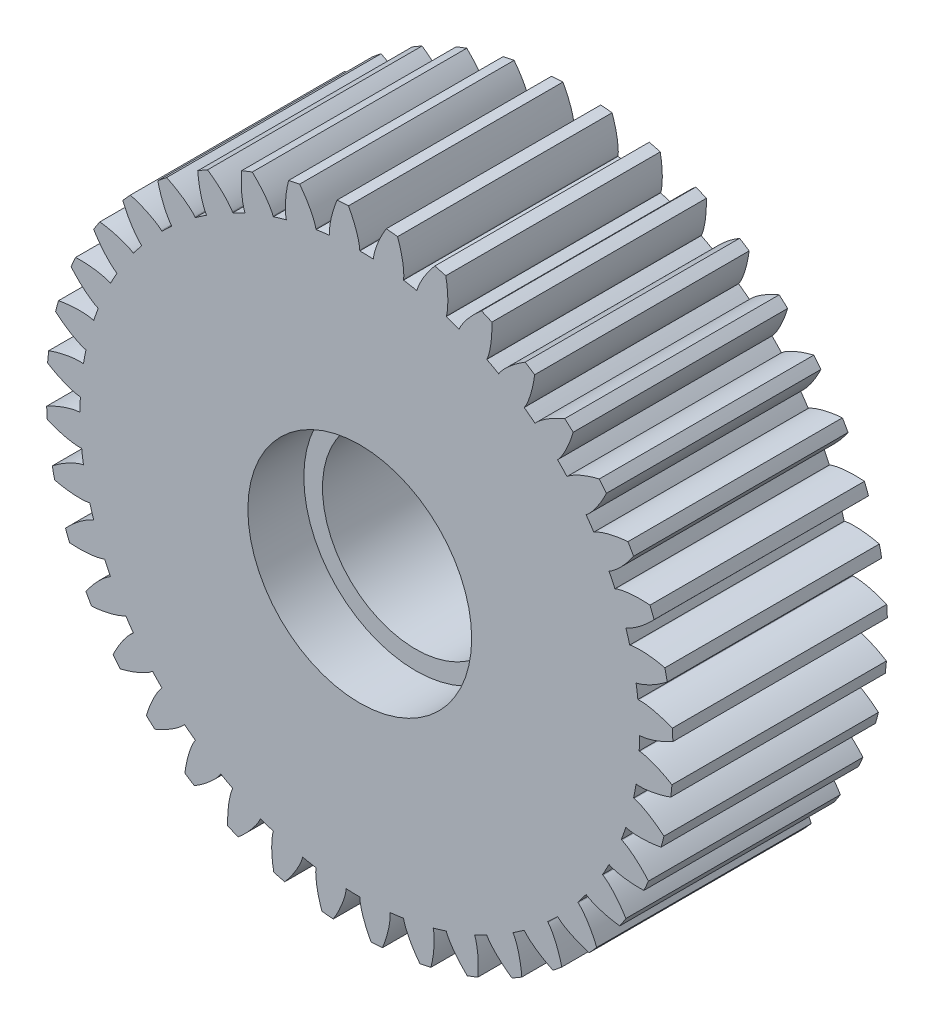
SolidWorks part; units mm, degrees
ref_plane "Front Plane" through (0, 0, 0) normal (0, 0, 1) x (1, 0, 0)
ref_plane "Top Plane" through (0, 0, 0) normal (0, 1, 0) x (1, 0, 0)
ref_plane "Right Plane" through (0, 0, 0) normal (1, 0, 0) x (0, 0, -1)
sketch "Sketch1" plane through (0, 0, 0) normal (0, 0, 1) x (1, 0, 0)
  circle A0 centre (0, 0) radius 16.8
  dimension "D1" = 33.6
extrude "Boss-Extrude1" add sketch "Sketch1" along normal mid plane 11.5
sketch "Sketch2" plane through (0, 0, 0) normal (0, 0, 1) x (1, 0, 0)
  line L0 (0, 0) -> (15.0351, 0) construction
  line L1 (0, 0) -> (15.9953, -0.3898) construction
  line L2 (0, 0) -> (15.0172, -0.7324) construction
  line L3 (15.0351, 0) -> (15, 0)
  line L4 (15.0172, -0.7324) -> (14.9822, -0.7307)
  circle A0 centre (0, 0) radius 16 construction
  circle A1 centre (0, 0) radius 15.0351 construction
  circle A2 centre (0, 0) radius 15
  circle A3 centre (0, 0) radius 16.8 construction
  circle A4 centre (0, 0) radius 16.8
  spline S0 degree 4 poles (15.0351, 0) (15.0402, 0.0001) (15.0546, 0.0005) (15.0819, 0.0022) (15.1262, 0.0063) (15.1827, 0.0135) (15.2554, 0.0248) (15.3409, 0.041) (15.4344, 0.0616) (15.5358, 0.0872) (15.6366, 0.1155) (15.7366, 0.1462) (15.8359, 0.1791) (15.9556, 0.2217) (16.0984, 0.2765) (16.2641, 0.346) (16.4505, 0.4312) (16.6387, 0.5248) (16.8223, 0.6224) (17.006, 0.7273) (17.1823, 0.8333) (17.3632, 0.9498) (17.5292, 1.0605) (17.7127, 1.1916) (17.86, 1.2993) (18.0514, 1.4488) (18.1637, 1.5393) (18.2939, 1.6477) (18.3513, 1.6972) (18.3866, 1.7276) knots 0 0 0 0 0 0.005377 0.015084 0.028532 0.04661 0.064855 0.092111 0.119476 0.146842 0.174209 0.201575 0.228941 0.256307 0.307035 0.361767 0.4165 0.471232 0.525964 0.580697 0.635429 0.690161 0.744894 0.799626 0.854358 0.909091 0.954545 1 1 1 1 1 construction
  spline S1 degree 4 poles (15.0351, 0) (15.0402, 0.0001) (15.0546, 0.0005) (15.0819, 0.0022) (15.1262, 0.0063) (15.1827, 0.0135) (15.2554, 0.0248) (15.3409, 0.041) (15.4344, 0.0616) (15.5358, 0.0872) (15.6366, 0.1155) (15.7366, 0.1462) (15.8359, 0.1791) (15.9556, 0.2217) (16.0984, 0.2765) (16.2641, 0.346) (16.4505, 0.4312) (16.6387, 0.5248) (16.8223, 0.6224) (17.006, 0.7273) (17.1823, 0.8333) (17.3632, 0.9498) (17.5292, 1.0605) (17.7127, 1.1916) (17.86, 1.2993) (18.0099, 1.4164) (18.0826, 1.4743) (18.1196, 1.5042) knots 0 0 0 0 0 0.005377 0.015084 0.028532 0.04661 0.064855 0.092111 0.119476 0.146842 0.174209 0.201575 0.228941 0.256307 0.307035 0.361767 0.4165 0.471232 0.525964 0.580697 0.635429 0.690161 0.744894 0.799626 0.854358 0.909091 0.909091 0.909091 0.909091 0.909091
  spline S2 degree 4 poles (15.0172, -0.7324) (15.0224, -0.7327) (15.0367, -0.7338) (15.0638, -0.7369) (15.108, -0.7432) (15.164, -0.753) (15.2361, -0.7679) (15.3207, -0.7882) (15.4131, -0.8134) (15.5131, -0.8439) (15.6124, -0.877) (15.7108, -0.9126) (15.8084, -0.9503) (15.9259, -0.9987) (16.0659, -1.0604) (16.228, -1.1379) (16.41, -1.232) (16.5934, -1.3347) (16.772, -1.4411) (16.9503, -1.5549) (17.1213, -1.6693) (17.2964, -1.7944) (17.4568, -1.9131) (17.6336, -2.053) (17.7755, -2.1678) (17.9594, -2.3264) (18.0671, -2.4223) (18.192, -2.5369) (18.2468, -2.5891) (18.2806, -2.6212) knots 0 0 0 0 0 0.005377 0.015084 0.028532 0.04661 0.064855 0.092111 0.119476 0.146842 0.174209 0.201575 0.228941 0.256307 0.307035 0.361767 0.4165 0.471232 0.525964 0.580697 0.635429 0.690161 0.744894 0.799626 0.854358 0.909091 0.954545 1 1 1 1 1 construction
  spline S3 degree 4 poles (15.0172, -0.7324) (15.0224, -0.7327) (15.0367, -0.7338) (15.0638, -0.7369) (15.108, -0.7432) (15.164, -0.753) (15.2361, -0.7679) (15.3207, -0.7882) (15.4131, -0.8134) (15.5131, -0.8439) (15.6124, -0.877) (15.7108, -0.9126) (15.8084, -0.9503) (15.9259, -0.9987) (16.0659, -1.0604) (16.228, -1.1379) (16.41, -1.232) (16.5934, -1.3347) (16.772, -1.4411) (16.9503, -1.5549) (17.1213, -1.6693) (17.2964, -1.7944) (17.4568, -1.9131) (17.6336, -2.053) (17.7755, -2.1678) (17.9196, -2.292) (17.9893, -2.3533) (18.0248, -2.385) knots 0 0 0 0 0 0.005377 0.015084 0.028532 0.04661 0.064855 0.092111 0.119476 0.146842 0.174209 0.201575 0.228941 0.256307 0.307035 0.361767 0.4165 0.471232 0.525964 0.580697 0.635429 0.690161 0.744894 0.799626 0.854358 0.909091 0.909091 0.909091 0.909091 0.909091
  dimension "D1" = 32
  dimension "D2" = 30.0702
  dimension "D3" = 30
  dimension "D4" = 1.396
  dimension "D5" = 1.396
extrude "Cut-Extrude1" cut sketch "Sketch2" against normal through all both and the other way through all contours A2 S3 A4 S1 region at (16.0514, -0.3912, 0)
pattern_circular "CirPattern2" count 40 over 360 about axis through (0, 0, 5.75) along (0, 0, -1) of "Cut-Extrude1"
sketch "Sketch3" plane through (0, 0, 5.75) normal (0, 0, 1) x (1, 0, 0)
  circle A0 centre (0, 0) radius 6
  dimension "D1" = 12
extrude "Cut-Extrude2" cut sketch "Sketch3" against normal blind 3
sketch "Sketch4" plane through (0, 0, 2.75) normal (0, 0, 1) x (1, 0, 0)
  circle A0 centre (0, 0) radius 5
  dimension "D1" = 10
extrude "Cut-Extrude3" cut sketch "Sketch4" against normal through all
mirror "Mirror1" about plane through (0, 0, 0) normal (0, 0, 1) of "Cut-Extrude2"
equation "\"Np\"= 40"
equation "\"module\"= 0.8"
equation "\"pressure angle\"= 20deg"
equation "\"h_a\"= 1 * \"module\"'addendum"
equation "\"h_b\"= 1.25 * \"module\"'dedendum"
equation "\"clr_tip_root\"= \"h_f\" - \"h_a\"'clearance of gear tooth tip and root"
equation "\"dp_p\"= \"module\" * \"Np\"'PCD"
equation "\"db_p\"= \"dp_p\" * cos ( \"pressure angle\" )'base CD"
equation "\"D1@Sketch1\"= \"dp_p\" + 2*\"h_a\" "
equation "\"fw_p\"= \"fw_r\""
equation "\"D1@Boss-Extrude1\"=\"fw_p\""
equation "\"D1@Sketch2\"=\"dp_p\""
equation "\"D2@Sketch2\"= \"db_p\""
equation "\"D3@Sketch2\"=\"dp_p\"- 2*\"h_b\""
equation "\"alpha_p\"= sqr ( \"dp_p\" ^ 2 - \"db_p\" ^ 2 ) / \"db_p\" * 180 / pi - \"pressure angle\""
equation "\"D4@Sketch2\"= 360 / ( 4 * \"Np\" ) - \"alpha_p\""
equation "\"beta_p\"= ( 360 / ( 4 * \"Np\" ) - \"alpha_p\" ) * 2"
equation "\"D5@Sketch2\"= 360 / ( 4 * \"Np\" ) - \"alpha_p\""
equation "\"D1@CirPattern2\"=\"Np\""
equation "\"Nr\"= \"Ns\" + 2 * \"Np\"'num teeth"
equation "\"pressure_angle\"= 20deg"
equation "\"h_f\"= 1.25 * \"module\"'dedendum"
equation "\"dp_r\"= \"module\" * \"Nr\"'PCD"
equation "\"db_r\"= \"dp_r\" * cos ( \"pressure_angle\" )'base CD"
equation "\"fw_r\"= 11.5mm'face width"
equation "\"alpha_r\"= sqr ( \"dp_r\" ^ 2 - \"db_r\" ^ 2 ) / \"db_r\" * 180 / pi - \"pressure_angle\""
equation "\"beta_r\"= ( 360 / ( 4 * \"Nr\" ) + \"alpha_r\" ) * 2"
equation "\"bearing_ID\"= \"module\" * ( \"Ns\" + \"Np\" ) + 10"
equation "\"bearing_OD\"= 1.18 * \"bearing_ID\" + 8.57"
equation "\"bearing_height\"= 0.09 * \"bearing_ID\" + 4.62"
equation "\"clearance_planet\"=1.5"
equation "\"case_dist\"= \"sec_carrier_thickness\" + \"clearance_planet\" + \"standard_clearance_1_5mm\""
equation "\"Motor_case_OD_max\"= \"case_mounting_PCD\" + \"case_mounting_hole_allen_socket_dia\" + \"clearance_case_mount_holes_shell_thickness\" * 2"
equation "\"case_mounting_PCD\"= \"motor_case_OD_base\" + \"case_mounting_hole_shift\" * 2"
equation "\"bearing mount thickness\"= IIF((\"bearing_OD\" + \"output_mounting_hole_dia\" * 4) > (\"Nr\" * \"module\" + 2 * \"h_b\"), \"output_mounting_hole_dia\" * 2, ((\"Nr\" * \"module\" + 2 * \"h_b\" - (\"bearing_OD\" + \"output_mounting_hole_dia\" * 4)) / 2) + \"output_mounting_hole_dia\" * 2 + \"standard_clearance_1_5mm\")"
equation "\"case_mounting_hole_dia\"=3"
equation "\"output_mounting_PCD\"= \"bearing_OD\" + \"bearing mount thickness\""
equation "\"output_mounting_hole_dia\"= 4"
equation "\"clearance_case_mount_holes_shell_thickness\"= 1"
equation "\"motor_case_OD_base\"= \"motor_OD\" + \"clearance_motor_and_case\" * 2 + \"Motor_case_thickness\" * 2"
equation "\"sec_carrier_thickness\"= 5"
equation "\"sun_coupler_hub_thickness\"= 4"
equation "\"clearance_sun_coupler_sec_carrier\"= 1.5"
equation "\"clearance_motor_and_case\"= IIF(\"ring_OD\" < \"motor_OD\", 5, (\"ring_OD\" - \"motor_OD\")/2 + 5)"
equation "\"motor_OD\"= 88.6"
equation "\"Motor_case_thickness\"= 2.5"
equation "\"Motor_case_ID\"= \"motor_OD\" + \"clearance_motor_and_case\" * 2"
equation "\"case_mounting_hole_shift\"= \"case_mounting_hole_dia\" / 2 - 0.5"
equation "\"output_mounting_nut_wrench_size\"= 7"
equation "\"output_mounting_nut_thickness\"= 3.2"
equation "\"case_mounting_hole_allen_socket_dia\"= 5.5"
equation "\"output_mounting_nut_depth\"= 3"
equation "\"case_mounting_bolt_depth\"= 4.5"
equation "\"Ns\"= 20"
equation "\"ring_radial_thickness\"= 5"
equation "\"ring_OD\"= \"Nr\" * \"module\" + \"ring_radial_thickness\" * 2"
equation "\"ring_to_chamfer_clearance\"= 2"
equation "\"Motor_case_OD_base_to_chamfer\"=5"
equation "\"pattern_offset_from_motor_case_OD_base\"= 3"
equation "\"pattern_bulge_dia\"= 3"
equation "\"pattern_num_bulge\"= 18"
equation "\"pattern_depth\"= 2"
equation "\"motor_height\"= 43"
equation "\"case_mounting_wrench_size\"= 5.5"
equation "\"case_mounting_nut_clearance\"= 2"
equation "\"base_plate_thickness\"= 4"
equation "\"case_mounting_nut_thickness\"= 2.4"
equation "\"case_mounting_surface_height\"= 4"
equation "\"motor_mount_hole_PCD\"= 32"
equation "\"motor_mount_hole_dia\"= 4"
equation "\"motor_mount_hole_num\"= 4"
equation "\"central_hole_offset_from_motor_mount_PCD\"= 5"
equation "\"wire_slot_dist_from_center\"= 30"
equation "\"wire_slot_length\"= 10"
equation "\"wire_slot_radius\"= 4"
equation "\"driver_upper_holes_dist_from_center\"= 23"
equation "\"driver_lower_holes_dist_from_center\"= 15"
equation "\"driver_side_holes_dist_from_center\"= 20"
equation "\"driver_mount_holes_dia\"= 2.5"
equation "\"driver_mount_inserts_OD\"= 3.5"
equation "\"driver_mount_thickness\"= 1.5"
equation "\"driver_mount_height\"= 4"
equation "\"air_flow_hole_offset\"= 3"
equation "\"num_planet\"= 3"
equation "\"planet_pin_bolt_dia\"= 5"
equation "\"planet_pin_socket_head_dia\"= 8.5"
equation "\"carrier_PCD\"= ( \"Np\" + \"Ns\" ) * \"module\""
equation "\"planet_shaft_dia\"= 8"
equation "\"planet_shaft_step_offset\"= 1"
equation "\"carrier_trapezoidal_support_sun_offset\"= 5"
equation "\"carrier_trapezoidal_support_hole_PCD_offset_bearing_ID\"= 4"
equation "\"carrier_trapezoidal_support_hole_dia\"= 3"
equation "\"carrier_trapezoidal_support_hole_socket_head_dia\"= 5.5"
equation "\"carrier_bearing_step_width\"= 1.5"
equation "\"standard_clearance_1_5mm\"=1.5"
equation "\"standard_fillet_1_5mm\"= 1.5"
equation "\"sun_shaft_bearing_OD\"= 16"
equation "\"sun_shaft_bearing_width\"= 4"
equation "\"standard_bearing_insertion_chamfer\"= 0.5"
equation "\"carrier_trapezoidal_support_hole_wrench_size\"= 5.5"
equation "\"planet_pin_bolt_wrench_size\"= 8"
equation "\"planet_bearing_OD\"= 12"
equation "\"planet_bearing_width\"= 3"
equation "\"planet_bore\"= 10"
equation "\"D1@Cut-Extrude2\"=\"carrier_trapezoidal_support_hole_dia\""
equation "\"D1@Sketch4\"=\"planet_bore\""
equation "\"motor_output_hole_PCD\"= 23"
equation "\"motor_output_hole_dia\"= 4"
equation "\"motor_output_hole_num\"= 4"
equation "\"dp_s\"= \"module\" * \"Ns\"'PCD"
equation "\"db_s\"= \"dp_s\" * cos ( \"pressure angle\" )'base CD"
equation "\"fw_s_calc\"= 13mm'face width"
equation "\"alpha_s\"= sqr ( \"dp_s\" ^ 2 - \"db_s\" ^ 2 ) / \"db_s\" * 180 / pi - \"pressure angle\""
equation "\"beta_s\"= ( 360 / ( 4 * \"Ns\" ) - \"alpha_s\" ) * 2"
equation "\"sun_shaft_bearing_ID\"= 8"
equation "\"sun_hub_dia\"= \"motor_output_hole_PCD\" + \"motor_output_hole_dia\" + \"standard_clearance_1_5mm\" * 4"
equation "\"sun_central_bolt_dia\"= 5"
equation "\"sun_central_bolt_socket_head_dia\"= 8.5"
equation "\"fw_s_used\"= \"fw_p\" + \"clearance_planet\" + \"sec_carrier_thickness\" + \"standard_clearance_1_5mm\""
equation "\"motor_output_hole_CSK_OD\"= 9'8.96 is exact value"
equation "\"motor_output_hole_CSK_head_height\"= 2.5"
equation "\"bearing_retainer_thickness\"= 2"
equation "\"D4@Sketch4\"=\"carrier_trapezoidal_support_sun_offset\""
equation "\"D2@Sketch5\"=\"carrier_trapezoidal_support_hole_dia\""
equation "\"D1@Sketch6\"=\"carrier_trapezoidal_support_hole_socket_head_dia\""
equation "\"D1@Cut-Extrude3\"=\"planet_pin_bolt_dia\""
equation "\"D1@Sketch7\"=\"planet_pin_socket_head_dia\""
equation "\"D1@Sketch9\"=\"sun_shaft_bearing_OD\""
equation "\"D1@Sketch10\"=\"standard_clearance_1_5mm\""
equation "\"D1@Sketch3\"= \"planet_bearing_OD\""
